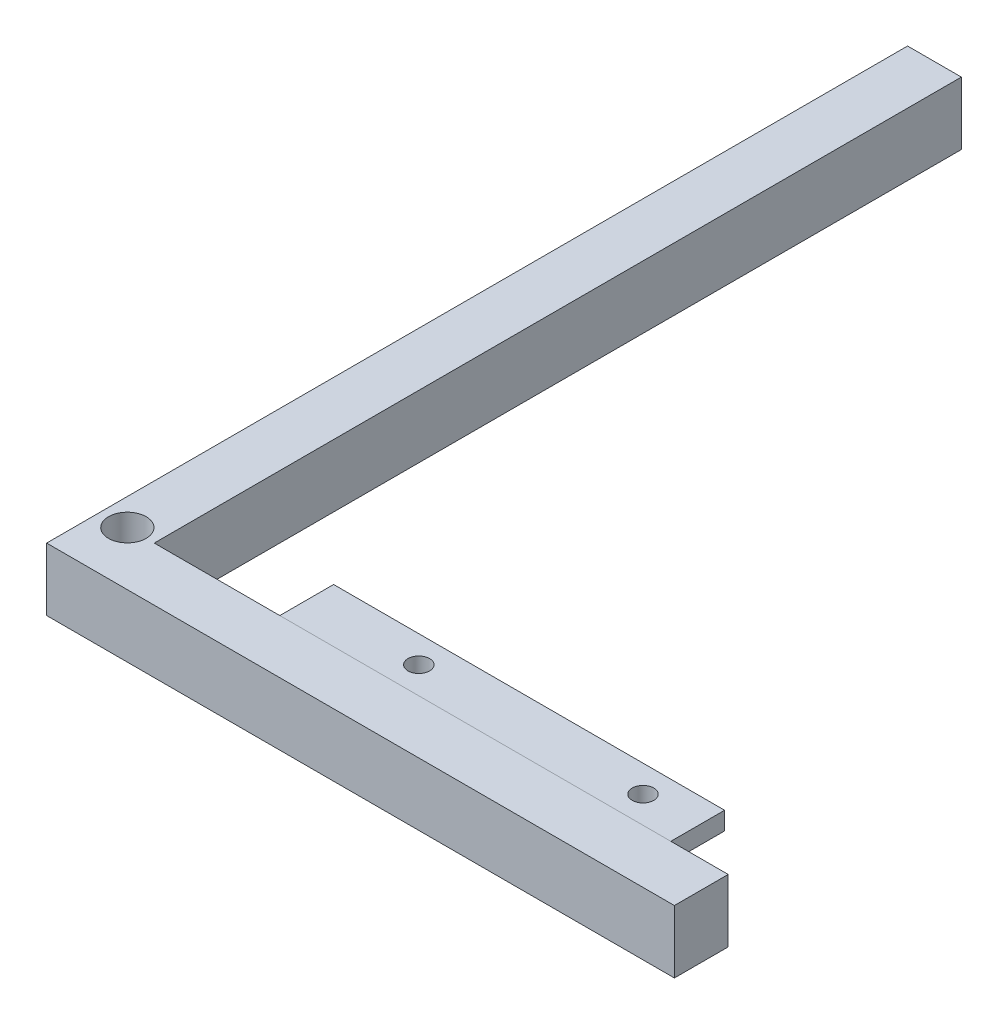
SolidWorks part; units mm, degrees
ref_plane "前视基准面" through (0, 0, 0) normal (0, 0, 1) x (1, 0, 0)
ref_plane "上视基准面" through (0, 0, 0) normal (0, 1, 0) x (1, 0, 0)
ref_plane "右视基准面" through (0, 0, 0) normal (1, 0, 0) x (0, 0, -1)
other "Configuration Table"
sketch "草图1" plane through (0, 0, 0) normal (0, 1, 0) x (1, 0, 0)
  line L1 (-17.5, -1.5) -> (17.5, -1.5)
  line L2 (-17.5, -1.5) -> (-17.5, 1.5)
  line L3 (-17.5, 1.5) -> (17.5, 1.5)
  line L4 (17.5, -1.5) -> (17.5, 1.5)
  line L5 (-17.5, -1.5) -> (17.5, 1.5) construction
  line L6 (-17.5, 1.5) -> (17.5, -1.5) construction
  line L7 (-17.5, 1.5) -> (-14.5, 1.5)
  line L8 (-17.5, 1.5) -> (-17.5, 46.5)
  line L9 (-17.5, 46.5) -> (-14.5, 46.5)
  line L10 (-14.5, 1.5) -> (-14.5, 46.5)
  point P0 (0, 0)
  dimension "D3" = 3
  dimension "D1" = 35
  dimension "D2" = 45
  dimension "D5" = 3
extrude "凸台-拉伸1" add sketch "草图1" along normal blind 3.5 contours L3 L4 L1 L2 | L7 L10 L9 L8
sketch "草图2" plane through (0, 0, 0) normal (0, -1, 0) x (1, 0, 0)
  line L0 (-16.5, -44.8) -> (-16.5, -3)
  line L1 (-16.5, -3) -> (-15.5, -3)
  line L2 (-15.5, -3) -> (-15.5, -44.8)
  line L3 (-15.5, -44.8) -> (-16.5, -44.8)
  line L4 (-17.5, 1.5) -> (-17.5, -46.5) construction
  line L5 (-17.5, -46.5) -> (-14.5, -46.5) construction
  line L6 (-17.5, 1.5) -> (17.5, 1.5) construction
  line L7 (-16, -0.5) -> (-16, 0.5)
  line L8 (-16, 0.5) -> (16, 0.5)
  line L9 (16, 0.5) -> (16, -0.5)
  line L10 (16, -0.5) -> (-16, -0.5)
  line L11 (17.5, 1.5) -> (17.5, -1.5) construction
  dimension "D1" = 1
  dimension "D2" = 1
  dimension "D3" = 1.7
  dimension "D4" = 4.5
  dimension "D5" = 1
  dimension "D6" = 1
  dimension "D7" = 1.5
  dimension "D8" = 1.5
extrude "切除-拉伸1" cut sketch "草图2" against normal blind 1.5
sketch "草图3" plane through (0, 3.5, 0) normal (0, 1, 0) x (1, 0, 0)
  line L0 (-17.5, -1.5) -> (17.5, -1.5) construction
  line L1 (-17.5, -1.5) -> (-17.5, 46.5) construction
  circle A0 centre (-16, 1.5) radius 0.6
  circle A1 centre (-16, 1.5) radius 1.05
  dimension "D2" = 1.2
  dimension "D3" = 2.1
  dimension "D1" = 3
  dimension "D4" = 1.5
extrude "切除-拉伸2" cut sketch "草图3" against normal through all contours A0
extrude "切除-拉伸5" cut sketch "草图3<4>" against normal blind 1.5 contours A1
sketch "草图3<4>" plane through (0, 3.5, 0) normal (0, 1, 0) x (1, 0, 0) same geometry as "草图3"
sketch "草图4" plane through (0, 0, 0) normal (0, -1, 0) x (1, 0, 0)
  line L0 (-14.5, -1.5) -> (17.5, -1.5) construction
  line L1 (-7.5, -1.5) -> (14.3, -1.5)
  line L2 (-7.5, -1.5) -> (-7.5, -4.5)
  line L3 (-7.5, -4.5) -> (14.3, -4.5)
  line L4 (14.3, -1.5) -> (14.3, -4.5)
  line L6 (17.5, 1.5) -> (17.5, -1.5) construction
  circle A0 centre (-1.25, -3) radius 0.6
  circle A1 centre (-1.25, -3) radius 1
  circle A2 centre (11.25, -3) radius 0.6
  circle A3 centre (11.25, -3) radius 1
  point P14 (0, 0)
  point P15 (0, 0)
  line M17 (-14.5, -1.5) -> (17.5, -1.5)
  dimension "D3" = 1.2
  dimension "D4" = 2
  dimension "D1" = 3
  dimension "D2" = 21.8
  dimension "D5" = 3.2
extrude "凸台-拉伸2" add sketch "草图4" along normal blind 1 from surface separate body contours L4 L2 L3 A3 A1 M17 | A1 A0 | A3 A2 region at (3.2299, 0, -3) region at (-2.2217, 0, -3) region at (10.2783, 0, -3) starting at face at (-16, 3.5, -0.45)
